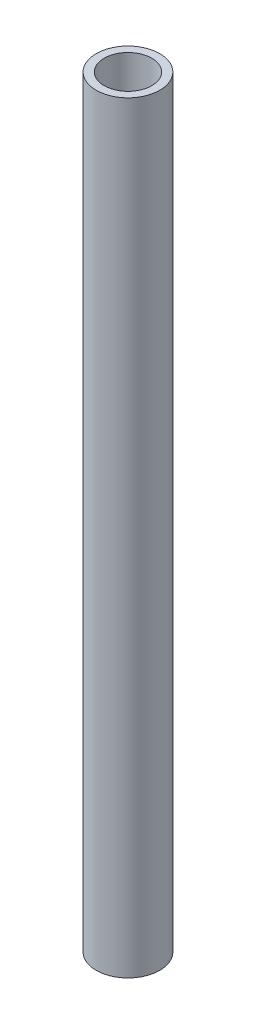
SolidWorks part; units mm, degrees
material "Custom Plastic"
ref_plane "X-Y Datum" through (0, 0, 0) normal (0, 0, 1) x (1, 0, 0)
ref_plane "X-Z Datum" through (0, 0, 0) normal (0, 1, 0) x (1, 0, 0)
ref_plane "Y-Z Datum" through (0, 0, 0) normal (1, 0, 0) x (0, 0, -1)
ref_point "Middle point"
sketch "Sketch2" plane through (0, 0, 0) normal (0, 1, 0) x (1, 0, 0)
  circle A0 centre (0, 0) radius 9.525
  circle A1 centre (0, 0) radius 12.7
  dimension "D2" = 19.05
extrude "Tube Stock - Extrude" add sketch "Sketch2" along normal blind 152.4 and the other way blind 152.4
equation "\"Torsion Tube Stock Outer Diameter\"= 1.0in"
equation "\"Torsion Tube Stock Wall Thickness\"= 0.25in"
equation "\"D1@Sketch2\"= \"Torsion Tube Stock Outer Diameter\""
equation "\"D2@Sketch2\"= \"Torsion Tube Stock Outer Diameter\" - \"Torsion Tube Stock Wall Thickness\""
equation "\"Torsion Tube Stock Length\"= 12in"
equation "\"D1@Tube Stock - Extrude\"=\"Torsion Tube Stock Length\"/2"
equation "\"D2@Tube Stock - Extrude\"=\"Torsion Tube Stock Length\"/2"
